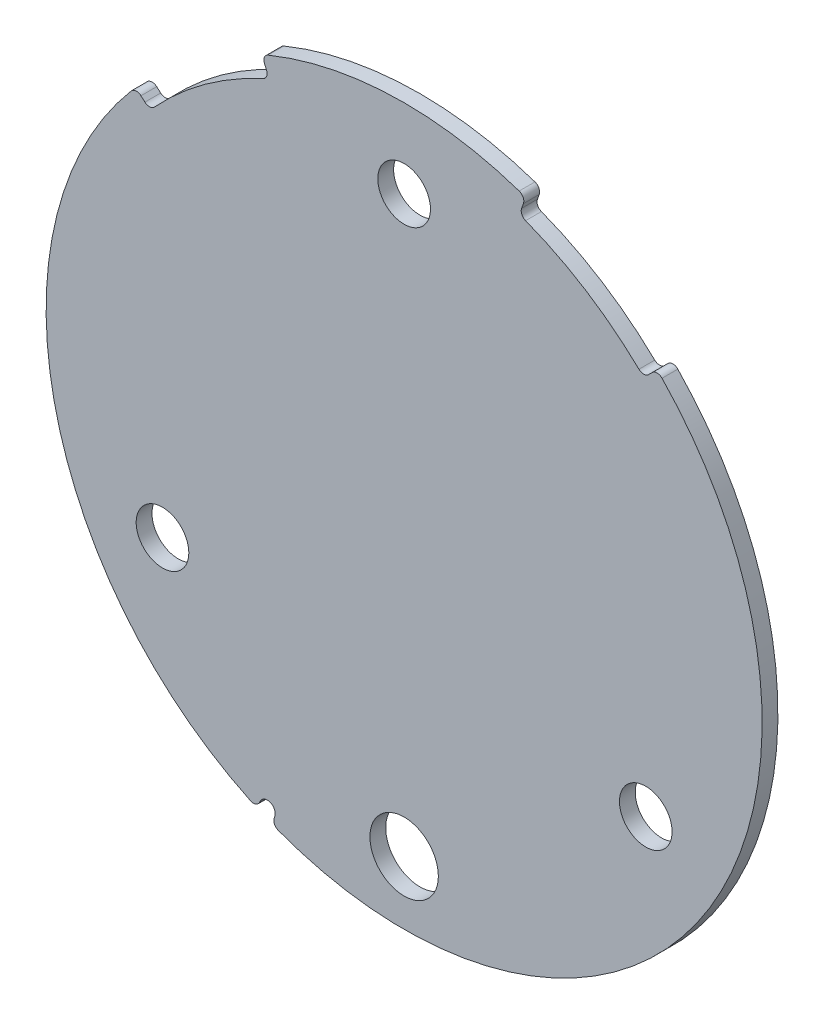
SolidWorks part; units mm, degrees
ref_plane "Alzado" through (0, 0, 0) normal (0, 0, 1) x (1, 0, 0)
ref_plane "Planta" through (0, 0, 0) normal (0, 1, 0) x (1, 0, 0)
ref_plane "Vista lateral" through (0, 0, 0) normal (1, 0, 0) x (0, 0, -1)
sketch "Model" plane through (0, 0, 0) normal (0, 0, 1) x (1, 0, 0)
  line L12 (23.9841, 23.7015) -> (20.8347, 18.3355)
  line L13 (20.8347, 18.3355) -> (9.1701, 24.9845)
  line L14 (9.1701, 24.9845) -> (11.9696, 30.4675)
  line L15 (11.9696, 30.4675) -> (23.9841, 23.7015)
  line L16 (23.5645, -22.1803) -> (11.6405, -29.0235)
  line L17 (11.6405, -29.0235) -> (8.6335, -23.7355)
  line L18 (8.6335, -23.7355) -> (20.4535, -16.8923)
  line L19 (20.4535, -16.8923) -> (23.5645, -22.1803)
  line L20 (-5.4405, -24.0979) -> (-8.4734, -29.4636)
  line L21 (-8.4734, -29.4636) -> (-20.5268, -22.4648)
  line L22 (-20.5268, -22.4648) -> (-17.5718, -17.1768)
  line L23 (-17.5718, -17.1768) -> (-5.4405, -24.0979)
  line L24 (6.9505, -26.589) -> (6.7665, -25.2108)
  line L25 (6.7665, -25.2108) -> (6.2386, -23.9493)
  line L26 (6.2386, -23.9493) -> (5.403, -22.8668)
  line L27 (5.403, -22.8668) -> (4.2959, -22.0254)
  line L28 (4.2959, -22.0254) -> (3.0068, -21.5041)
  line L29 (3.0068, -21.5041) -> (1.6493, -21.3393)
  line L30 (1.6493, -21.3393) -> (0.2952, -21.5305)
  line L31 (0.2952, -21.5305) -> (-0.9834, -22.077)
  line L32 (-0.9834, -22.077) -> (-2.0739, -22.9397)
  line L33 (-2.0739, -22.9397) -> (-2.8882, -24.0384)
  line L34 (-2.8882, -24.0384) -> (-3.3914, -25.31)
  line L35 (-3.3914, -25.31) -> (-3.5485, -26.6915)
  line L36 (-4.4685, -32.0246) -> (-3.5485, -26.6915)
  line L37 (7.8915, -32.0205) -> (11.0678, -31.275)
  line L38 (11.0678, -31.275) -> (14.108, -30.2492)
  line L39 (14.108, -30.2492) -> (16.9999, -28.9593)
  line L40 (16.9999, -28.9593) -> (19.7314, -27.4213)
  line L41 (19.7314, -27.4213) -> (22.2902, -25.6513)
  line L42 (22.2902, -25.6513) -> (24.6641, -23.6655)
  line L43 (24.6641, -23.6655) -> (26.841, -21.4799)
  line L44 (26.841, -21.4799) -> (28.8088, -19.1106)
  line L45 (28.8088, -19.1106) -> (30.5551, -16.5737)
  line L46 (30.5551, -16.5737) -> (32.0679, -13.8853)
  line L47 (32.0679, -13.8853) -> (33.3349, -11.0616)
  line L48 (33.3349, -11.0616) -> (34.344, -8.1185)
  line L49 (34.344, -8.1185) -> (35.083, -5.0721)
  line L50 (35.083, -5.0721) -> (35.5397, -1.9387)
  line L51 (35.5397, -1.9387) -> (35.702, 1.2658)
  line L52 (35.702, 1.2658) -> (35.5575, 4.5252)
  line L53 (35.5575, 4.5252) -> (35.105, 7.7563)
  line L54 (35.105, 7.7563) -> (34.3609, 10.8774)
  line L55 (34.3609, 10.8774) -> (33.3403, 13.875)
  line L56 (33.3403, 13.875) -> (32.058, 16.7354)
  line L57 (32.058, 16.7354) -> (30.5289, 19.445)
  line L58 (30.5289, 19.445) -> (28.7681, 21.9903)
  line L59 (28.7681, 21.9903) -> (26.7902, 24.3576)
  line L60 (26.7902, 24.3576) -> (24.6104, 26.5334)
  line L61 (24.6104, 26.5334) -> (22.2435, 28.504)
  line L62 (22.2435, 28.504) -> (19.7044, 30.2558)
  line L63 (19.7044, 30.2558) -> (17.008, 31.7752)
  line L64 (17.008, 31.7752) -> (14.1693, 33.0487)
  line L65 (14.1693, 33.0487) -> (11.2032, 34.0627)
  line L66 (11.2032, 34.0627) -> (8.1245, 34.8034)
  line L67 (8.1245, 34.8034) -> (4.9482, 35.2574)
  line L68 (4.9482, 35.2574) -> (1.6892, 35.411)
  line L69 (1.6892, 35.411) -> (-1.5698, 35.2552)
  line L70 (-1.5698, 35.2552) -> (-4.7458, 34.7991)
  line L71 (-4.7458, 34.7991) -> (-7.824, 34.0563)
  line L72 (-7.824, 34.0563) -> (-10.7894, 33.0405)
  line L73 (-10.7894, 33.0405) -> (-13.6273, 31.7651)
  line L74 (-13.6273, 31.7651) -> (-16.3227, 30.2438)
  line L75 (-16.3227, 30.2438) -> (-18.8606, 28.4903)
  line L76 (-18.8606, 28.4903) -> (-21.2262, 26.5182)
  line L77 (-21.2262, 26.5182) -> (-23.4046, 24.341)
  line L78 (-23.4046, 24.341) -> (-25.3808, 21.9723)
  line L79 (-25.3808, 21.9723) -> (-27.14, 19.4259)
  line L80 (-27.14, 19.4259) -> (-28.6673, 16.7153)
  line L81 (-28.6673, 16.7153) -> (-29.9477, 13.854)
  line L82 (-29.9477, 13.854) -> (-30.9663, 10.8558)
  line L83 (-30.9663, 10.8558) -> (-31.7083, 7.7341)
  line L84 (-31.7083, 7.7341) -> (-32.1587, 4.5028)
  line L85 (-32.1587, 4.5028) -> (-32.301, 1.2432)
  line L86 (-32.301, 1.2432) -> (-32.1366, -1.9611)
  line L87 (-32.1366, -1.9611) -> (-31.6779, -5.0943)
  line L88 (-31.6779, -5.0943) -> (-30.9369, -8.1401)
  line L89 (-30.9369, -8.1401) -> (-29.9258, -11.0825)
  line L90 (-29.9258, -11.0825) -> (-28.6569, -13.9055)
  line L91 (-28.6569, -13.9055) -> (-27.1423, -16.5929)
  line L92 (-27.1423, -16.5929) -> (-25.3943, -19.1286)
  line L93 (-25.3943, -19.1286) -> (-23.425, -21.4966)
  line L94 (-23.425, -21.4966) -> (-21.2466, -23.6807)
  line L95 (-21.2466, -23.6807) -> (-18.8713, -25.665)
  line L96 (-18.8713, -25.665) -> (-16.3114, -27.4332)
  line L97 (-16.3114, -27.4332) -> (-13.5789, -28.9694)
  line L98 (-13.5789, -28.9694) -> (-10.6861, -30.2574)
  line L99 (-10.6861, -30.2574) -> (-7.6453, -31.2812)
  line L100 (-7.6453, -31.2812) -> (-4.4685, -32.0246)
  line L101 (6.9505, -26.589) -> (7.8915, -32.0205)
  point P1 (-4.4685, -32.0246)
  point P2 (-10.7894, 33.0405)
sketch "Croquis3" plane through (0, 0, 0) normal (0, 0, 1) x (1, 0, 0)
  line L0 (-19.3008, -18.5746) -> (-7.1406, -25.5122) construction
  line L1 (-19.3008, -18.5746) -> (-22.3732, -23.9598) construction
  line L2 (-7.1406, -25.5122) -> (-10.213, -30.8974) construction
  line L3 (-22.3732, -23.9598) -> (-10.213, -30.8974) construction
  line L4 (6.9334, -25.1498) -> (19.0493, -18.1352) construction
  line L5 (6.9334, -25.1498) -> (10.0398, -30.5154) construction
  line L6 (19.0493, -18.1352) -> (22.1558, -23.5009) construction
  line L7 (10.0398, -30.5154) -> (22.1558, -23.5009) construction
  line L8 (10.2361, 28.9943) -> (22.4348, 22.1246) construction
  line L9 (10.2361, 28.9943) -> (7.1938, 23.592) construction
  line L10 (22.4348, 22.1246) -> (19.3925, 16.7223) construction
  line L11 (7.1938, 23.592) -> (19.3925, 16.7223) construction
  line L12 (0, 0) -> (0, -28.0037) construction
  line L13 (0, 0) -> (-6.3752, -33.4001) construction
  line L14 (-5.1573, -27.0193) -> (-6.2808, -32.9053)
  line L15 (5.1573, -27.0193) -> (6.2808, -32.9053)
  line L31 (7.4092, 23.4707) -> (7.7711, 24.617) construction
  circle A0 centre (0, 0) radius 34.0031 construction
  circle A1 centre (0, -28.0037) radius 5.2504 construction
  arc A2 (-5.1573, -27.0193) -> (5.1573, -27.0193) centre (0, -28.0037) cw
  arc A3 (-6.873, -33.3012) -> (6.873, -33.3012) centre (0, 0) cw
  arc A5 (-6.2808, -32.9053) -> (-6.873, -33.3012) centre (-6.7719, -32.8115) cw
  arc A6 (6.2808, -32.9053) -> (6.873, -33.3012) centre (6.7719, -32.8115) ccw
  point P0 (-5.1573, -27.0193)
  dimension "D13" = 68.0062
  dimension "D14" = 10.5008
  dimension "D16" = 0.5
  dimension "D1" = 28.0037
  dimension "D2" = 6.2
  dimension "D3" = 14
  dimension "D4" = 18.5746
  dimension "D5" = 18.1352
  dimension "D6" = 16.7223
  dimension "D7" = 23.592
  dimension "D8" = 25.5122
  dimension "D9" = 25.1498
  dimension "D10" = 7.1938
  dimension "D11" = 6.9334
  dimension "D12" = 7.1406
extrude "Saliente-Extruir2" add sketch "Croquis3" along normal blind 1.5
sketch "Croquis5" plane through (0, 0, 0) normal (0, 0, 1) x (1, 0, 0)
  circle A0 centre (0, -28.0037) radius 5.2504 construction
  circle A1 centre (0, 0) radius 34.0031 construction
  circle A2 centre (0, -28.0037) radius 5.2504 construction
  circle A3 centre (0, 0) radius 34.0031
  circle A4 centre (0, -28.0037) radius 3.25
  dimension "D1" = 6.5
extrude "Saliente-Extruir3" add sketch "Croquis5" along normal blind 1.5 contours A3 | A4
sketch "Croquis4" plane through (0, 0, 0) normal (0, 0, 1) x (1, 0, 0)
  line L0 (10.2361, 28.9943) -> (22.4348, 22.1246) construction
  line L1 (22.4348, 22.1246) -> (19.3925, 16.7223) construction
  line L2 (7.1938, 23.592) -> (19.3925, 16.7223) construction
  line L3 (10.2361, 28.9943) -> (7.1938, 23.592) construction
  line L4 (10.2361, 28.9943) -> (22.4348, 22.1246) construction
  line L5 (22.4348, 22.1246) -> (19.3925, 16.7223) construction
  line L6 (7.1938, 23.592) -> (19.3925, 16.7223) construction
  line L7 (10.2361, 28.9943) -> (7.1938, 23.592) construction
  line L24 (0, 0) -> (17.263, 27.1851) construction
  line L26 (22.7594, 22.7826) -> (24.0316, 24.056)
  line L27 (10.941, 30.2875) -> (11.5525, 31.9804)
  arc A0 (6.873, -33.3012) -> (-6.873, -33.3012) centre (0, 0) ccw construction
  arc A1 (24.0316, 24.056) -> (11.5525, 31.9804) centre (0, 0) ccw
  arc A2 (10.941, 30.2875) -> (22.7594, 22.7826) centre (0, 0) cw
  point P14 (16.0978, -27.0081)
  point P19 (17.263, 27.1851)
  dimension "D4" = 34.0031
  dimension "D1" = 14
  dimension "D3" = 1.8
  dimension "D2" = 32.2031
extrude "Cortar-Extruir6" cut sketch "Croquis4" along normal blind 1.5
fillet "Redondeo2" radius 0.65 4 edges at (11.5525, 31.9804, 0.75) (24.0316, 24.056, 0.75) (22.7594, 22.7826, 0.75) (10.941, 30.2875, 0.75)
ref_axis "Eje1" through (0, 0, -0.075) along (0, 0, 1)
pattern_circular "MatrizC2" [suppressed] count 2 every 182 about axis through (0, 0, -0.075) along (0, 0, 1) of bodies 111
pattern_circular "MatrizC3" [suppressed] count 2 every 243 about axis through (0, 0, -0.075) along (0, 0, 1) of bodies 113
sketch "Croquis6" plane through (0, 0, 1.5) normal (0, 0, 1) x (1, 0, 0)
  line L0 (0, 0) -> (-19.9865, 27.5091) construction
  line L1 (-24.1372, 21.3128) -> (-25.4888, 22.5063)
  line L2 (-12.8109, 29.5418) -> (-13.5283, 31.1961)
  line L3 (0, 0) -> (0, 35.0983) construction
  line L5 (11.1596, 30.8928) -> (11.3295, 31.3631)
  line L6 (23.5677, 23.5917) -> (23.2143, 23.2379)
  arc A0 (10.9271, 32.1995) -> (24.4958, 23.5831) centre (0, 0) ccw construction
  arc A1 (-24.1372, 21.3128) -> (-12.8109, 29.5418) centre (0, 0) cw
  arc A9 (11.3295, 31.3631) -> (10.9271, 32.1995) centre (10.7182, 31.584) ccw
  arc A10 (10.9271, 32.1995) -> (24.4958, 23.5831) centre (0, 0) ccw
  arc A11 (24.4958, 23.5831) -> (23.5677, 23.5917) centre (24.0276, 23.1323) ccw
  arc A12 (22.3042, 23.2284) -> (23.2143, 23.2379) centre (22.7544, 23.6973) ccw
  arc A13 (22.3042, 23.2284) -> (11.5381, 30.0651) centre (0, 0) ccw
  arc A14 (11.1596, 30.8928) -> (11.5381, 30.0651) centre (11.771, 30.672) ccw
  arc A16 (-13.5283, 31.1961) -> (-25.4888, 22.5063) centre (0, 0) ccw
  point P16 (-18.9267, 26.0503)
  dimension "D1" = 0
  dimension "D4" = 32.2
  dimension "D2" = 14
  dimension "D3" = 36
extrude "Cortar-Extruir7" cut sketch "Croquis6" against normal blind 1.5
fillet "Redondeo3" radius 0.65 4 edges at (-24.1372, 21.3128, 0.75) (-13.5283, 31.1961, 0.75) (-12.8109, 29.5418, 0.75) (-25.4888, 22.5063, 0.75)
sketch "Croquis7" plane through (0, 0, 1.5) normal (0, 0, 1) x (1, 0, 0)
  line L0 (0, 0) -> (-13.2861, -31.3) construction
  line L1 (-13.9886, -30.9924) -> (-13.6766, -30.3011)
  line L2 (-13.6766, -30.3011) -> (0, 0) construction
  line L3 (-12.5767, -31.5917) -> (-12.2962, -30.887)
  line L4 (0, 0) -> (0, -34.0031) construction
  arc A0 (-25.9225, 22.0053) -> (24.4958, 23.5831) centre (0, 0) ccw construction
  arc A1 (-12.2962, -30.887) -> (-13.6766, -30.3011) centre (-12.993, -30.6096) ccw
  arc A2 (-12.5767, -31.5917) -> (-13.9886, -30.9924) centre (0, 0) cw
  arc M12 (-25.9225, 22.0053) -> (24.4958, 23.5831) centre (0, 0) ccw
  dimension "D1" = 1.5
  dimension "D2" = 0.75
  dimension "D3" = 23
extrude "Cortar-Extruir8" cut sketch "Croquis7" against normal blind 1.5 contours L3 A1 L1 M12 region at (-13.0209, -30.6752, 1.5)
fillet "Redondeo4" radius 0.65 2 edges at (-12.5767, -31.5917, 0.75) (-13.9886, -30.9924, 0.75)
sketch "Croquis9" plane through (0, 0, 0) normal (0, 0, 1) x (1, 0, 0)
  line L0 (0, 0) -> (0, 26.5) construction
  line L1 (0, 0) -> (0, 26.5) construction
  circle A0 centre (0, 26.5) radius 2.5
  circle A1 centre (22.9497, -13.25) radius 2.5
  circle A2 centre (-22.9497, -13.25) radius 2.5
  dimension "D2" = 5
  dimension "D1" = 26.5
  dimension "D4" = 26.5
  dimension "D3" = 3
extrude "Cortar-Extruir10" cut sketch "Croquis9" along normal through all contours A2 | A1 | A0 region at (-22.9497, -13.25, 0)
equation "\"D2@Croquis4\"=\"D4@Croquis4\"-1.8"
equation "\"D2@Croquis7\"=\"D1@Croquis7\"/2"
